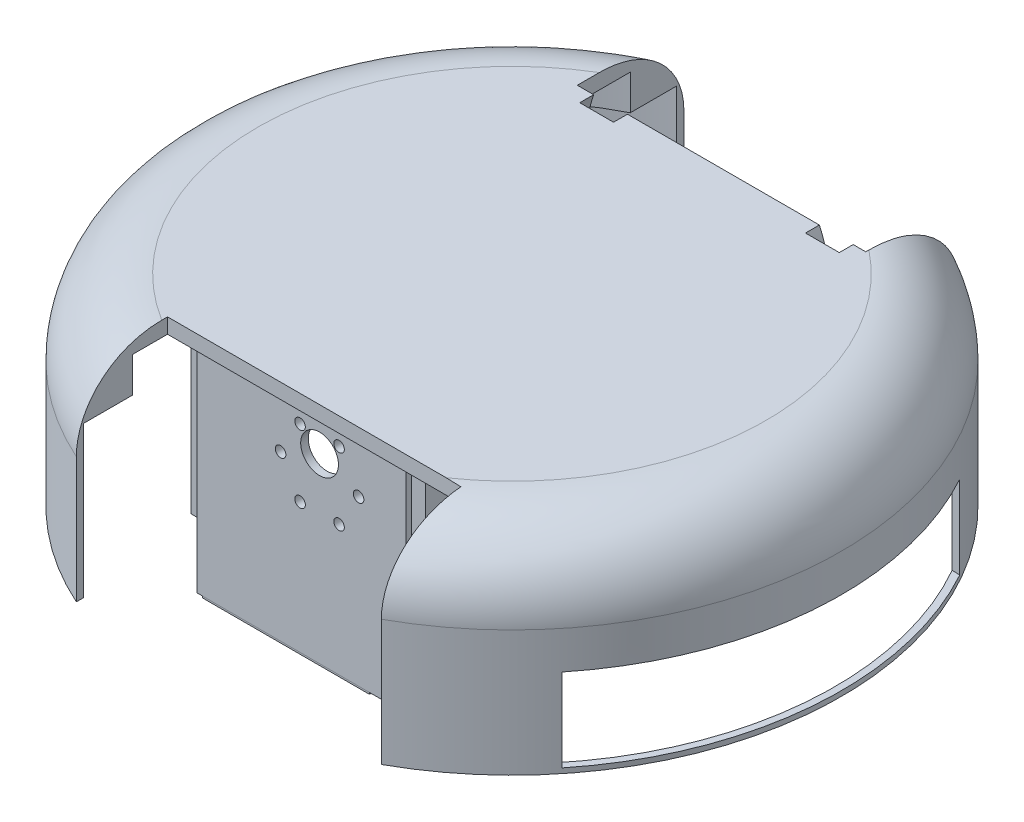
SolidWorks part; units mm, degrees
ref_plane "Front Plane" through (0, 0, 0) normal (0, 0, 1) x (1, 0, 0)
ref_plane "Top Plane" through (0, 0, 0) normal (0, 1, 0) x (1, 0, 0)
ref_plane "Right Plane" through (0, 0, 0) normal (1, 0, 0) x (0, 0, -1)
sketch "MotorHoldersSketch" plane through (0, 0, 0) normal (0, 0, 1) x (1, 0, 0)
  line L0 (0, 0) -> (170, 0) construction
  line L1 (0, 0) -> (0, 23.41) construction
  line L2 (170, 0) -> (170, 23.41) construction
  circle A1 centre (170, 0) radius 23.41
ref_axis "MotorCenterAxis1" through (0, 0, 0) along (0, 0, 1)
ref_axis "MotorCenterAxis2" through (170, 0, 0) along (0, 0, 1)
extrude "MotorHolders" add sketch "MotorHoldersSketch" along normal blind 80 and the other way blind 80
sketch "Sketch3" plane through (0, 0, 0) normal (0, 0, 1) x (1, 0, 0)
  line L1 (1.9406, 21.133) -> (168.3435, 21.133)
  line L2 (1.9406, 21.133) -> (1.9406, 18.3155)
  line L3 (1.9406, 18.3155) -> (168.3435, 18.3155)
  line L4 (168.3435, 21.133) -> (168.3435, 18.3155)
sketch "Sketch4" plane through (0, 0, 0) normal (0, 1, 0) x (1, 0, 0)
  line L1 (221.2811, -76.3794) -> (-41.4939, -76.3794)
  line L2 (221.2811, -76.3794) -> (221.2811, 76.7331)
  line L3 (221.2811, 76.7331) -> (-41.4939, 76.7331)
  line L4 (-41.4939, -76.3794) -> (-41.4939, 76.7331)
extrude "Cut-Extrude1" cut sketch "Sketch4" against normal blind 26
ref_axis "Axis3" through (170, 0, 0) along (0, -1, 0)
sketch3d "ReferencePlanePosition"
  line L0 (170, 0, 0) -> (170, -34.8293, 0)
  line L1 (170, 0, 0) -> (170, -38.994, 0) construction
ref_plane "ReferencePlane" through (170, -34.8293, 0) normal (0, -1, 0) x (-1, 0, 0)
sketch3d "3DSketch3"
  line L0 (170, 0, 0) -> (170, -64.5, 0) construction
ref_plane "Plane2" through (170, -64.5, 0) normal (0, -1, 0) x (-1, 0, 0)
sketch "Sketch7" plane through (170, -64.5, 0) normal (0, -1, 0) x (-1, 0, 0)
  line L1 (-9.5047, -80.801) -> (181.32, -80.801)
  line L2 (-9.5047, -80.801) -> (-9.5047, 73.8662)
  line L3 (-9.5047, 73.8662) -> (181.32, 73.8662)
  line L4 (181.32, -80.801) -> (181.32, 73.8662)
  line L5 (151.8712, -54.3972) -> (26.5361, -54.3972)
  line L6 (151.8712, -54.3972) -> (151.8712, 46.2413)
  line L7 (151.8712, 46.2413) -> (26.5361, 46.2413)
  line L8 (26.5361, -54.3972) -> (26.5361, 46.2413)
ref_point "Point1"
sketch "MotorHolderExtrudeSketch" plane through (0, 0, 0) normal (0, 0, 1) x (1, 0, 0)
  circle A0 centre (170, 0) radius 20.415
  circle A4 centre (170, 0) radius 23.41 construction
ref_point "TopOfMotors"
ref_plane "TangentToTopOfMotors" through (0, -20.415, 0) normal (0, 1, 0) x (1, 0, 0)
ref_plane "BottomOfPowerBankRegion" through (0, -20.425, 0) normal (0, 1, 0) x (1, 0, 0)
ref_plane "BottomPlane" through (0, 19.575, 0) normal (0, 1, 0) x (1, 0, 0)
sketch "Sketch21" plane through (0, 19.575, 0) normal (0, 1, 0) x (1, 0, 0)
  line L0 (219.6842, -79.5488) -> (-50.341, -79.5488) construction
  line L1 (-50.341, -79.5488) -> (-50.341, 79.7899) construction
  line L2 (-50.341, 79.7899) -> (219.6842, 79.7899) construction
  line L3 (219.6842, 79.7899) -> (219.6842, -79.5488) construction
  circle A1 centre (163.8303, 2.6392) radius 131
  point P2 (166.9941, 0)
  point P5 (163.8303, 2.6392)
extrude "BottomPlate" add sketch "Sketch21" along normal blind 5 and the other way blind 75
sketch "Sketch53" plane through (0, -55.425, 0) normal (0, -1, 0) x (1, 0, 0)
  circle A0 centre (163.8303, -2.6392) radius 128.3241
extrude "BottomPlateCutForTheInside" cut sketch "Sketch53" against normal offset from surface (60 mm away) 20 up to face at (163.8303, 24.575, 128.3608)
fillet "Fillet2" radius 30 1 edges at (163.8303, 24.575, 128.3608) type face fillet first side face at (163.8303, -55.425, 128.3608) second side face at (163.8303, 24.575, 128.3608)
sketch "Sketch57" plane through (0, 4.575, 0) normal (0, -1, 0) x (1, 0, 0)
  circle A0 centre (161.7307, -3.0914) radius 110.3746
  point P2 (161.7307, -3.0914)
extrude "CutForTheInside2" cut sketch "Sketch57" against normal blind 14
ref_point "CenterAtBottomOfPowerBank"
ref_plane "TopOfPowerBankPlane" through (0, -54.425, 0) normal (0, 1, 0) x (1, 0, 0)
sketch "Sketch13" plane through (0, -54.425, 0) normal (0, 1, 0) x (1, 0, 0)
  line L1 (-19.4498, 72.5454) -> (166.1636, 72.5454)
  line L2 (-19.4498, 72.5454) -> (-19.4498, -78.2051)
  line L3 (-19.4498, -78.2051) -> (166.1636, -78.2051)
  line L4 (166.1636, 72.5454) -> (166.1636, -78.2051)
  line L5 (19.3173, -49.583) -> (137.9607, -49.583)
  line L6 (19.3173, -49.583) -> (19.3173, -21.0549)
  line L7 (19.3173, -21.0549) -> (137.9607, -21.0549)
  line L8 (137.9607, -49.583) -> (137.9607, -21.0549)
  line L9 (19.3173, 56.6778) -> (137.9607, 56.6778)
  line L10 (19.3173, 56.6778) -> (19.3173, 36.3234)
  line L11 (19.3173, 36.3234) -> (137.9607, 36.3234)
  line L12 (137.9607, 56.6778) -> (137.9607, 36.3234)
  line L13 (19.3173, 18.3186) -> (137.9607, 18.3186)
  line L14 (19.3173, 18.3186) -> (19.3173, -7.3615)
  line L15 (19.3173, -7.3615) -> (137.9607, -7.3615)
  line L16 (137.9607, 18.3186) -> (137.9607, -7.3615)
sketch "Sketch15" plane through (150.0096, 0, 0) normal (1, 0, 0) x (0, 0, -1)
  line L1 (72.5313, -25.7765) -> (45.7099, -25.7765)
  line L2 (72.5313, -25.7765) -> (72.5313, -24.2242)
  line L3 (72.5313, -24.2242) -> (45.7099, -24.2242)
  line L4 (45.7099, -25.7765) -> (45.7099, -24.2242)
ref_plane "Plane6" through (0, 0, 0) normal (0, 0, 1) x (1, 0, 0)
sketch "MotorGeometry1" plane through (0, 0, 0) normal (0, 0, 1) x (1, 0, 0)
  line L0 (170, 0) -> (170, -13.42)
  line L1 (170, 0) -> (170, -34.8293) construction
  line L2 (170, -13.42) -> (162.25, -13.42) construction
  line L3 (170, -13.42) -> (177.75, -13.42) construction
  line L4 (170, -13.42) -> (170, 7) construction
  line L5 (170, 0) -> (185.5, 0) construction
  line L6 (170, 0) -> (154.5, 0) construction
  line L7 (170, 0) -> (170, 13.42) construction
  line L8 (170, 0) -> (170, 23.41) construction
  line L9 (170, 13.42) -> (177.75, 13.42) construction
  line L10 (170, 13.42) -> (162.25, 13.42)
ref_axis "BoltAxisA" through (185.5, 0, 0) along (0, 0, 1)
ref_axis "BoltAxisB" through (177.75, -13.42, 0) along (0, 0, 1)
ref_axis "BoltAxisC" through (162.25, -13.42, 0) along (0, 0, 1)
ref_axis "BoltAxisD" through (154.5, 0, 0) along (0, 0, 1)
ref_axis "BoltAxisE" through (162.25, 13.42, 0) along (0, 0, 1)
ref_axis "BoltAxisF" through (177.75, 13.42, 0) along (0, 0, 1)
ref_point "Point6"
ref_point "Point7"
ref_point "Point8"
ref_point "Point9"
ref_point "Point10"
ref_point "Point11"
ref_point "Point12"
ref_point "Point13"
ref_point "Point14"
ref_point "Point15"
ref_point "Point16"
ref_point "Point17"
ref_point "Point35"
ref_axis "OutputShaftReference2" through (170, 7, 0) along (0, 0, 1)
ref_plane "HoleReferencePlane1" through (0, 0, 80) normal (0, 0, 1) x (1, 0, 0)
ref_point "OutputShaftPosition3"
sketch "Sketch23" plane through (0, 0, 80) normal (0, 0, 1) x (1, 0, 0)
  line L5 (121.3218, 21.8402) -> (204.258, 21.8402)
  line L6 (121.3218, 21.8402) -> (121.3218, -65.2231)
  line L7 (121.3218, -65.2231) -> (204.258, -65.2231)
  line L8 (204.258, 21.8402) -> (204.258, -65.2231)
extrude "MotorMountingSupport1" add sketch "Sketch23" against normal blind 6
ref_plane "HoleReferencePlane2" through (0, 0, -80) normal (0, 0, -1) x (-1, 0, 0)
ref_point "OutputShaftPosition4"
sketch "Sketch24" plane through (0, 0, -80) normal (0, 0, -1) x (-1, 0, 0)
  line L1 (-202.1905, -67.1257) -> (-139.5471, -67.1257)
  line L2 (-202.1905, -67.1257) -> (-202.1905, 19.2374)
  line L3 (-202.1905, 19.2374) -> (-139.5471, 19.2374)
  line L4 (-139.5471, -67.1257) -> (-139.5471, 19.2374)
extrude "MotorMountingSuppor2" add sketch "Sketch24" against normal blind 6
sketch "Sketch17" plane through (0, 0, 80) normal (0, 0, 1) x (1, 0, 0)
  circle A0 centre (185.5, 0) radius 2.1
  circle A1 centre (177.75, -13.42) radius 2.1
  circle A2 centre (162.25, -13.42) radius 2.1
  circle A3 centre (154.5, 0) radius 2.1
  circle A4 centre (162.25, 13.42) radius 2.1
  circle A5 centre (177.75, 13.42) radius 2.1
  circle A6 centre (170, 7) radius 7.5
extrude "MotorHoles1" cut sketch "Sketch17" against normal blind 31.5
sketch "Sketch19" plane through (0, 0, -80) normal (0, 0, -1) x (-1, 0, 0)
  circle A0 centre (-185.5, 0) radius 2.1
  circle A1 centre (-177.75, -13.42) radius 2.1
  circle A2 centre (-162.25, -13.42) radius 2.1
  circle A3 centre (-154.5, 0) radius 2.1
  circle A4 centre (-162.25, 13.42) radius 2.1
  circle A5 centre (-177.75, 13.42) radius 2.1
  circle A6 centre (-170, 7) radius 7.5
extrude "Cut-Extrude4" cut sketch "Sketch19" against normal blind 30
ref_plane "Front" through (219.0581, 0, 0) normal (1, 0, 0) x (0, 0, -1)
sketch "Sketch29" plane through (219.0581, 0, 0) normal (1, 0, 0) x (0, 0, -1)
  line L1 (76.6955, -63.9254) -> (-77.9397, -63.9254)
  line L2 (76.6955, -63.9254) -> (76.6955, 20.2062)
  line L3 (76.6955, 20.2062) -> (-77.9397, 20.2062)
  line L4 (-77.9397, -63.9254) -> (-77.9397, 20.2062)
  line L5 (-13.4507, -48.1531) -> (12.5493, -48.1531)
  line L6 (-13.4507, -48.1531) -> (-13.4507, -28.9404)
  line L7 (-13.4507, -28.9404) -> (12.5493, -28.9404)
  line L8 (12.5493, -48.1531) -> (12.5493, -28.9404)
ref_plane "Plane12" through (0, -64.8293, 0) normal (0, -1, 0) x (-1, 0, 0)
sketch "Sketch28" plane through (0, -64.8293, 0) normal (0, -1, 0) x (-1, 0, 0)
  line L1 (-189.3897, -79.549) -> (-123.0026, -79.549)
  line L2 (-189.3897, -79.549) -> (-189.3897, 78.1499)
  line L3 (-189.3897, 78.1499) -> (-123.0026, 78.1499)
  line L4 (-123.0026, -79.549) -> (-123.0026, 78.1499)
extrude "CellPhonePlate" add sketch "Sketch28" along normal blind 1.5 and the other way blind 2.5
extrude "MotorHolderCut" cut sketch "MotorHolderExtrudeSketch" against normal blind 77 and the other way blind 77
sketch "Sketch31" plane through (219.0581, 0, 0) normal (1, 0, 0) x (0, 0, -1)
  line L0 (49.4417, -6.1927) -> (49.4417, -19.3739)
  line L1 (49.4417, -19.3739) -> (42.9342, -21.6341)
  line L2 (42.9342, -21.6341) -> (40.0618, -21.6341)
  line L3 (40.0618, -21.6341) -> (37.7863, -19.3586)
  line L4 (37.7863, -19.3586) -> (37.7863, -15.3813)
  line L5 (37.7863, -15.3813) -> (40.0618, -13.1059)
  line L6 (40.0618, -13.1059) -> (37.7863, -6.5545)
  line L7 (37.7863, -6.5545) -> (41.498, -6.5545)
  line L8 (41.498, -6.5545) -> (43.4004, -12.0319)
  line L9 (43.4004, -12.0319) -> (46.389, -12.0319)
  line L10 (46.389, -12.0319) -> (46.389, -6.5545)
  line L11 (46.389, -6.5545) -> (49.4417, -6.1927)
  line L12 (33.0193, -21.6341) -> (33.0193, -9.8302)
  line L13 (33.0193, -9.8302) -> (30.5402, -7.3511)
  line L14 (30.5402, -7.3511) -> (25.7203, -7.3511)
  line L15 (25.7203, -7.3511) -> (23.2412, -9.8302)
  line L16 (23.2412, -9.8302) -> (23.2412, -21.6341)
  line L17 (23.2412, -21.6341) -> (25.7203, -21.6341)
  line L18 (25.7203, -21.6341) -> (25.7203, -10.7454)
  line L19 (25.7203, -10.7454) -> (30.5402, -10.7454)
  line L20 (30.5402, -10.7454) -> (30.5402, -21.6341)
  line L21 (30.5402, -21.6341) -> (33.0193, -21.6341)
  line L22 (19.7226, -8.5907) -> (19.7226, -21.6341)
  line L23 (19.7226, -21.6341) -> (13.8207, -15.7322)
  line L24 (13.8207, -15.7322) -> (13.8207, -21.6341)
  line L25 (13.8207, -21.6341) -> (10.7708, -21.6341)
  line L26 (10.7708, -21.6341) -> (10.7708, -8.5907)
  line L27 (10.7708, -8.5907) -> (16.7716, -14.5915)
  line L28 (16.7716, -14.5915) -> (16.7716, -8.5907)
  line L29 (16.7716, -8.5907) -> (19.7226, -8.5907)
  line L30 (7.3891, -8.5907) -> (7.3891, -21.6341)
  line L31 (7.3891, -21.6341) -> (3.7282, -21.6341)
  line L32 (3.7282, -21.6341) -> (1.3209, -17.37)
  line L33 (1.3209, -17.37) -> (-1.2519, -21.6341)
  line L34 (-1.2519, -21.6341) -> (-3.6554, -21.6341)
  line L35 (-3.6554, -21.6341) -> (-4.6916, -8.5907)
  line L36 (-4.6916, -8.5907) -> (-2.4537, -8.5907)
  line L37 (-2.4537, -8.5907) -> (0.0345, -15.7545)
  line L38 (0.0345, -15.7545) -> (1.3209, -13.6224)
  line L39 (1.3209, -13.6224) -> (4.8544, -15.7545)
  line L40 (4.8544, -15.7545) -> (4.8544, -8.5907)
  line L41 (4.8544, -8.5907) -> (7.3891, -8.5907)
  line L42 (-7.6823, -21.6341) -> (-10.9875, -15.7545)
  line L43 (-10.9875, -15.7545) -> (-10.9875, -8.5907)
  line L44 (-10.9875, -8.5907) -> (-15.3102, -8.5907)
  line L45 (-15.3102, -8.5907) -> (-15.3102, -15.7545)
  line L46 (-15.3102, -15.7545) -> (-19.2695, -21.6341)
  line L47 (-19.2695, -21.6341) -> (-15.3102, -21.6341)
  line L48 (-15.3102, -21.6341) -> (-13.1489, -18.4245)
  line L49 (-13.1489, -18.4245) -> (-10.9875, -22.2693)
  line L50 (-10.9875, -22.2693) -> (-7.6823, -21.6341)
  line L51 (46.389, -17.8857) -> (46.389, -14.5915)
  line L52 (46.389, -14.5915) -> (41.498, -14.5915)
  line L53 (41.498, -14.5915) -> (39.5067, -16.2541)
  line L54 (39.5067, -16.2541) -> (41.5656, -18.7201)
  line L55 (41.5656, -18.7201) -> (46.389, -17.8857)
  line L56 (-22.571, -8.5907) -> (-22.0989, -21.6341)
  line L57 (-22.0989, -21.6341) -> (-26.4915, -21.6341)
  line L58 (-26.4915, -21.6341) -> (-29.9116, -19.3586)
  line L59 (-29.9116, -19.3586) -> (-30.636, -15.7545)
  line L60 (-30.636, -15.7545) -> (-27.4135, -14.1052)
  line L61 (-27.4135, -14.1052) -> (-30.636, -8.5907)
  line L62 (-30.636, -8.5907) -> (-27.4135, -8.5907)
  line L63 (-27.4135, -8.5907) -> (-25.3987, -14.1052)
  line L64 (-25.3987, -14.1052) -> (-24.2952, -14.1052)
  line L65 (-24.2952, -14.1052) -> (-24.4948, -8.5907)
  line L66 (-24.4948, -8.5907) -> (-22.571, -8.5907)
  line L67 (-35.0099, -8.5907) -> (-38.6395, -8.5907)
  line L68 (-38.6395, -8.5907) -> (-41.5241, -13.6224)
  line L69 (-41.5241, -13.6224) -> (-41.5241, -18.4245)
  line L70 (-41.5241, -18.4245) -> (-38.6395, -21.3091)
  line L71 (-38.6395, -21.3091) -> (-35.0099, -21.3091)
  line L72 (-35.0099, -21.3091) -> (-32.4978, -18.797)
  line L73 (-32.4978, -18.797) -> (-32.4978, -14.1052)
  line L74 (-32.4978, -14.1052) -> (-35.0099, -8.5907)
  line L75 (-44.0593, -21.3091) -> (-44.0593, -8.5907)
  line L76 (-44.0593, -8.5907) -> (-49.4499, -8.5907)
  line L77 (-49.4499, -8.5907) -> (-52.2269, -11.3677)
  line L78 (-52.2269, -11.3677) -> (-52.2269, -14.1052)
  line L79 (-52.2269, -14.1052) -> (-50.5777, -15.7545)
  line L80 (-50.5777, -15.7545) -> (-52.2269, -17.4037)
  line L81 (-52.2269, -17.4037) -> (-52.2269, -19.3586)
  line L82 (-52.2269, -19.3586) -> (-49.4499, -21.3091)
  line L83 (-49.4499, -21.3091) -> (-44.0593, -21.3091)
  line L84 (-57.7977, -21.3091) -> (-55.6011, -19.1125)
  line L85 (-55.6011, -19.1125) -> (-55.6011, -10.7454)
  line L86 (-55.6011, -10.7454) -> (-59.2637, -8.5907)
  line L87 (-59.2637, -8.5907) -> (-61.7818, -8.5907)
  line L88 (-61.7818, -8.5907) -> (-63.9365, -10.7454)
  line L89 (-63.9365, -10.7454) -> (-63.9365, -19.1125)
  line L90 (-63.9365, -19.1125) -> (-61.7818, -21.2672)
  line L91 (-61.7818, -21.2672) -> (-57.7977, -21.3091)
  line L92 (-66.7918, -21.2672) -> (-74.8705, -21.2672)
  line L93 (-74.8705, -21.2672) -> (-74.8705, -19.1125)
  line L94 (-74.8705, -19.1125) -> (-72.2665, -19.1125)
  line L95 (-72.2665, -19.1125) -> (-72.2665, -8.5907)
  line L96 (-72.2665, -8.5907) -> (-69.9977, -8.5907)
  line L97 (-69.9977, -8.5907) -> (-69.9977, -19.1125)
  line L98 (-69.9977, -19.1125) -> (-66.7918, -19.1125)
  line L99 (-66.7918, -19.1125) -> (-66.7918, -21.2672)
  line L100 (-36.1114, -18.797) -> (-34.7181, -17.4037)
  line L101 (-34.7181, -17.4037) -> (-34.7181, -13.1059)
  line L102 (-34.7181, -13.1059) -> (-36.6627, -11.1613)
  line L103 (-36.6627, -11.1613) -> (-37.8659, -11.1613)
  line L104 (-37.8659, -11.1613) -> (-39.3107, -13.1059)
  line L105 (-39.3107, -13.1059) -> (-39.5155, -16.8544)
  line L106 (-39.5155, -16.8544) -> (-38.25, -18.7201)
  line L107 (-38.25, -18.7201) -> (-36.1114, -18.797)
  line L108 (-46.2436, -16.8544) -> (-48.9032, -16.8544)
  line L109 (-48.9032, -16.8544) -> (-49.4499, -18.4245)
  line L110 (-49.4499, -18.4245) -> (-48.0836, -19.3586)
  line L111 (-48.0836, -19.3586) -> (-46.2436, -19.3586)
  line L112 (-46.2436, -19.3586) -> (-46.2436, -16.8544)
  line L113 (-45.9206, -14.5915) -> (-45.9206, -11.1613)
  line L114 (-45.9206, -11.1613) -> (-49.2105, -10.7454)
  line L115 (-49.2105, -10.7454) -> (-50.1756, -12.8764)
  line L116 (-50.1756, -12.8764) -> (-48.5891, -14.5915)
  line L117 (-48.5891, -14.5915) -> (-45.9206, -14.5915)
  line L118 (-58.5672, -18.7201) -> (-57.7977, -17.4037)
  line L119 (-57.7977, -17.4037) -> (-57.7977, -11.7636)
  line L120 (-57.7977, -11.7636) -> (-59.6573, -10.7454)
  line L121 (-59.6573, -10.7454) -> (-60.8144, -10.7454)
  line L122 (-60.8144, -10.7454) -> (-62.101, -12.0319)
  line L123 (-62.101, -12.0319) -> (-61.7818, -17.4037)
  line L124 (-61.7818, -17.4037) -> (-60.8144, -18.7201)
  line L125 (-60.8144, -18.7201) -> (-58.5672, -18.7201)
  line L126 (-24.2952, -19.3586) -> (-24.2952, -16.2541)
  line L127 (-24.2952, -16.2541) -> (-26.4915, -16.2541)
  line L128 (-26.4915, -16.2541) -> (-27.4135, -17.1761)
  line L129 (-27.4135, -17.1761) -> (-27.4135, -18.4245)
  line L130 (-27.4135, -18.4245) -> (-26.3339, -19.5041)
  line L131 (-26.3339, -19.5041) -> (-24.2952, -19.3586)
sketch "Sketch54" plane through (0, 18.575, 0) normal (0, -1, 0) x (1, 0, 0)
  line L1 (214.4412, -78.0789) -> (199.5357, -78.0789)
  line L2 (214.4412, -78.0789) -> (214.4412, -60.3349)
  line L3 (214.4412, -60.3349) -> (199.5357, -60.3349)
  line L4 (199.5357, -78.0789) -> (199.5357, -60.3349)
  line L5 (144.7348, -61.6331) -> (133.1116, -61.6331)
  line L6 (144.7348, -61.6331) -> (144.7348, -77.0397)
  line L7 (144.7348, -77.0397) -> (133.1116, -77.0397)
  line L8 (133.1116, -61.6331) -> (133.1116, -77.0397)
  line L9 (209.7798, 57.4342) -> (194.3676, 57.4342)
  line L10 (209.7798, 57.4342) -> (209.7798, 77.7709)
  line L11 (209.7798, 77.7709) -> (194.3676, 77.7709)
  line L12 (194.3676, 57.4342) -> (194.3676, 77.7709)
  line L13 (116.7119, 49.2746) -> (131.707, 49.2746)
  line L14 (116.7119, 49.2746) -> (116.7119, 77.7709)
  line L15 (116.7119, 77.7709) -> (131.707, 77.7709)
  line L16 (131.707, 49.2746) -> (131.707, 77.7709)
extrude "Boss-Extrude12" add sketch "Sketch54" along normal blind 60
sketch "Sketch11" plane through (0, -20.425, 0) normal (0, 1, 0) x (1, 0, 0)
  line L0 (-125.013, 7.5612) -> (295.013, -7.5612) construction
  line L5 (55.0389, -72.8934) -> (55.0389, 75.0508)
  line L6 (295.013, 65.2564) -> (295.013, -80.3788)
  line L7 (295.013, -80.3788) -> (55.0389, -72.8934)
  line L8 (295.013, 65.2564) -> (55.0389, 75.0508)
  point P0 (85, 0)
extrude "PowerBankCut" cut sketch "Sketch11" against normal blind 33
sketch "Sketch37" plane through (0, -20.425, 0) normal (0, -1, 0) x (1, 0, 0)
  line L1 (144.416, -35.6729) -> (89.0759, -35.6729)
  line L2 (144.416, -35.6729) -> (144.416, -65.4438)
  line L3 (144.416, -65.4438) -> (89.0759, -65.4438)
  line L4 (89.0759, -35.6729) -> (89.0759, -65.4438)
sketch "Sketch42" plane through (0, 0, 80) normal (0, 0, 1) x (1, 0, 0)
  circle A0 centre (170, 7) radius 42
  circle A1 centre (170, 7) radius 54.5
sketch "Sketch43" plane through (0, 0, -80) normal (0, 0, -1) x (-1, 0, 0)
  circle A0 centre (-170, 7) radius 42
  circle A1 centre (-170, 7) radius 54.5
extrude "Cut-Extrude11" cut sketch "Sketch43" against normal blind 5 and the other way blind 10
sketch "Sketch46" plane through (0, 4.575, 0) normal (0, -1, 0) x (1, 0, 0)
  line L1 (226.7934, 80.6381) -> (110.1992, 80.6381)
  line L2 (226.7934, 80.6381) -> (226.7934, 206.3319)
  line L3 (226.7934, 206.3319) -> (110.1992, 206.3319)
  line L4 (110.1992, 80.6381) -> (110.1992, 206.3319)
  line L5 (226.5792, -192.0075) -> (111.9219, -192.0075)
  line L6 (226.5792, -192.0075) -> (226.5792, -80.526)
  line L7 (226.5792, -80.526) -> (111.9219, -80.526)
  line L8 (111.9219, -192.0075) -> (111.9219, -80.526)
sketch "Sketch49" plane through (0, 0, 81.6459) normal (0, 0, 1) x (1, 0, 0)
  line L1 (202.543, 24.6365) -> (128.7027, 24.6365)
  line L2 (202.543, 24.6365) -> (202.543, -21.4682)
  line L3 (202.543, -21.4682) -> (128.7027, -21.4682)
  line L4 (128.7027, 24.6365) -> (128.7027, -21.4682)
extrude "Cut-Extrude15" cut sketch "Sketch19<2>" against normal blind 20 contours A2 | A3 | A4 | A0 | A1 | A5 | A6 rebuild error yes
sketch "Sketch19<2>" plane through (0, 0, -80) normal (0, 0, -1) x (-1, 0, 0) same geometry as "Sketch19"
sketch "Sketch52" plane through (0, -55.425, 0) normal (0, -1, 0) x (1, 0, 0)
  circle A0 centre (163.8303, -2.6392) radius 134.2142
extrude "WheelOpenings" cut sketch "Sketch46" against normal through all and the other way through all
sketch "Sketch55" plane through (0, -55.425, 0) normal (0, -1, 0) x (1, 0, 0)
  line L1 (82.1576, 79.7165) -> (-28.7155, 79.7165)
  line L2 (82.1576, 79.7165) -> (82.1576, -76.582)
  line L3 (82.1576, -76.582) -> (-28.7155, -76.582)
  line L4 (-28.7155, 79.7165) -> (-28.7155, -76.582)
extrude "Cut-Extrude23" cut sketch "Sketch55" against normal blind 45 and the other way blind 5
sketch "Sketch56" plane through (0, 4.575, 0) normal (0, -1, 0) x (1, 0, 0)
  circle A0 centre (166.6581, 0) radius 112.0768
  point P2 (157.1319, -15.3414)
  point P3 (158.3651, -11.7994)
  point P4 (166.6581, 0)
